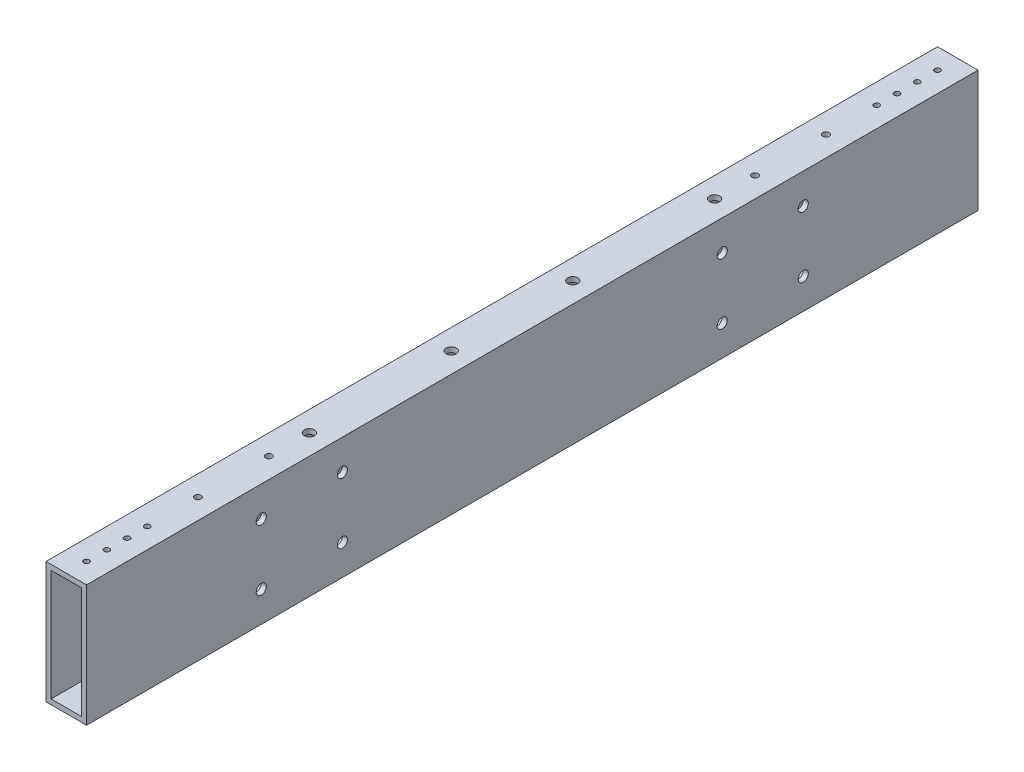
SolidWorks part; units mm, degrees
ref_plane "Front Plane" through (0, 0, 0) normal (0, 0, 1) x (1, 0, 0)
ref_plane "Top Plane" through (0, 0, 0) normal (0, 1, 0) x (1, 0, 0)
ref_plane "Right Plane" through (0, 0, 0) normal (1, 0, 0) x (0, 0, -1)
sketch "Sketch1" plane through (0, 0, 0) normal (0, 0, 1) x (1, 0, 0)
  line L0 (9.525, 34.925) -> (-9.525, 34.925)
  line L1 (12.7, 38.1) -> (-12.7, 38.1)
  line L2 (12.7, 38.1) -> (12.7, -38.1)
  line L3 (12.7, -38.1) -> (-12.7, -38.1)
  line L4 (-12.7, 38.1) -> (-12.7, -38.1)
  line L5 (12.7, 38.1) -> (-12.7, -38.1) construction
  line L6 (12.7, -38.1) -> (-12.7, 38.1) construction
  line L7 (-9.525, 34.925) -> (-9.525, -34.925)
  line L8 (9.525, -34.925) -> (-9.525, -34.925)
  line L9 (9.525, 34.925) -> (9.525, -34.925)
  point P0 (0, 0)
  dimension "D1" = 76.2
  dimension "D2" = 25.4
  dimension "D3" = 3.175
extrude "Boss-Extrude1" add sketch "Sketch1" along normal mid plane 558.8
sketch "Sketch2" plane through (0, 38.1, 0) normal (0, 1, 0) x (1, 0, 0)
  line L0 (12.7, 279.4) -> (-12.7, 279.4) construction
  line L1 (66.7546, 0) -> (-110.9827, 0) construction
  line L2 (12.7, -279.4) -> (-12.7, -279.4) construction
  circle A0 centre (0, 266.7) radius 1.7272
  circle A1 centre (0, 254) radius 1.7272
  circle A2 centre (0, 241.3) radius 1.7272
  circle A3 centre (0, 228.6) radius 1.7272
  circle A4 centre (0, -266.7) radius 1.7272
  circle A5 centre (0, -254) radius 1.7272
  circle A6 centre (0, -241.3) radius 1.7272
  circle A7 centre (0, -228.6) radius 1.7272
  circle A9 centre (0, -241.3) radius 1.7272
  point P22 (0, -279.4)
  point P26 (0, 279.4)
  dimension "D1" = 3.4544
  dimension "D4" = 3.4544
  dimension "D2" = 12.7
  dimension "D5" = 12.7
  dimension "D6" = 12.7
  dimension "D3" = 4
sketch "Sketch3" plane through (0, -38.1, 0) normal (0, -1, 0) x (1, 0, 0)
  line L2 (9.525, 279.4) -> (-9.525, 279.4) construction
  circle A0 centre (0, 266.7) radius 1.7272
  circle A1 centre (0, 241.3) radius 1.7272
  circle A2 centre (0, 215.9) radius 1.7272
  circle A3 centre (0, 190.5) radius 1.7272
  circle A4 centre (0, 165.1) radius 1.7272
  circle A5 centre (0, 139.7) radius 1.7272
  circle A6 centre (0, 114.3) radius 1.7272
  circle A7 centre (0, 88.9) radius 1.7272
  circle A8 centre (0, 63.5) radius 1.7272
  circle A9 centre (0, 38.1) radius 1.7272
  circle A10 centre (0, 12.7) radius 1.7272
  circle A11 centre (0, -12.7) radius 1.7272
  circle A12 centre (0, -38.1) radius 1.7272
  circle A13 centre (0, -63.5) radius 1.7272
  circle A14 centre (0, -88.9) radius 1.7272
  circle A15 centre (0, -114.3) radius 1.7272
  circle A16 centre (0, -139.7) radius 1.7272
  circle A17 centre (0, -165.1) radius 1.7272
  circle A18 centre (0, -190.5) radius 1.7272
  circle A19 centre (0, -215.9) radius 1.7272
  circle A20 centre (0, -241.3) radius 1.7272
  circle A21 centre (0, -266.7) radius 1.7272
  point P6 (0, 279.4)
  dimension "D1" = 3.4544
  dimension "D2" = 12.7
  dimension "D4" = 25.4
  dimension "D3" = 22
extrude "Cut-Extrude2" cut sketch "Sketch3" against normal blind 6.35
hole_wizard "1/4 (0.25) Diameter Hole1" positions "Sketch9" profile "Sketch8" hole size "1/4" standard "ANSI Inch"
sketch "Sketch9" plane through (-12.7, 0, 0) normal (-1, 0, 0) x (0, 0, 1)
  line L0 (-119.0625, -19.05) -> (119.0625, -19.05) construction
  line L2 (279.4, -38.1) -> (-279.4, -38.1) construction
  line L3 (279.4, 38.1) -> (-279.4, 38.1) construction
  line L4 (-127, 0) -> (127, 0) construction
  point P10 (-119.0625, -19.05)
  point P11 (119.0625, -19.05)
  point P25 (-119.0625, 19.05)
  point P27 (119.0625, 19.05)
  point P34 (0, -19.05)
  point P168 (169.8625, 19.05)
  point P170 (169.8625, -19.05)
  point P174 (-169.8625, 19.05)
  point P176 (-169.8625, -19.05)
  dimension "D1" = 238.125
  dimension "D2" = 19.05
  dimension "D3" = 254
  dimension "D4" = 19.05
  dimension "D5" = 19.05
  dimension "D6" = 50.8
  dimension "D7" = 50.8
sketch "Sketch8" plane through (-12.7, -19.05, -119.0625) normal (0, 1, 0) x (0, 0, 1)
  line L0 (0, 0) -> (0, 27.3077)
  line L1 (0, 27.3077) -> (3.175, 25.4)
  line L2 (3.175, 25.4) -> (3.175, 0)
  line L5 (3.175, 0) -> (0, 0)
  line L10 (0, 27.3077) -> (-3.175, 25.4) construction
  line L11 (0, -6.35) -> (0, 107.95) construction
  dimension "Hole Dia." = 6.35
  dimension "Hole Depth" = 25.4
  dimension "Drill Angle" = 118
hole_wizard "1/4 (0.25) Diameter Hole2" positions "Sketch12" profile "Sketch13" hole size "1/4" standard "ANSI Inch" end condition through all
sketch "Sketch12" plane through (0, 38.1, 0) normal (0, 1, 0) x (1, 0, 0)
  line L0 (12.7, -279.4) -> (-12.7, -279.4) construction
  line L1 (0, 38.1) -> (0, -38.1) construction
  point P2 (0, 127)
  point P7 (0, -127)
  point P20 (0, -38.1)
  point P22 (0, 38.1)
  point P27 (0, -279.4)
  point P32 (0, 0)
  dimension "D1" = 127
  dimension "D2" = 127
  dimension "D7" = 76.2
sketch "Sketch13" plane through (0, 38.1, -127) normal (1, 0, 0) x (0, 0, 1)
  line L0 (0, 0) -> (0, 76.2)
  line L1 (0, 76.2) -> (3.175, 76.2)
  line L2 (3.175, 76.2) -> (3.175, 0)
  line L5 (3.175, 0) -> (0, 0)
  line L11 (0, -6.35) -> (0, 107.95) construction
  dimension "Thru Hole Dia." = 6.35
  dimension "Thru Hole Depth" = 76.2
extrude "Cut-Extrude3" cut sketch "Sketch2" against normal blind 5.08 contours A0 | A1 | A2 | A3 | A4 | A5 | A6 | A7 region at (0, 38.1, -266.7) region at (0, 38.1, -254) region at (0, 38.1, -241.3) region at (0, 38.1, -228.6) region at (0, 38.1, 266.7) region at (0, 38.1, 254) region at (0, 38.1, 241.3) region at (0, 38.1, 228.6)
hole_wizard "#10-32 Tapped Hole1" positions "Sketch15" profile "Sketch14" tap size "#10-32" standard "ANSI Inch"
sketch "Sketch15" plane through (0, 38.1, 0) normal (0, 1, 0) x (1, 0, 0)
  line L0 (12.7, 279.4) -> (-12.7, 279.4) construction
  line L1 (12.7, -279.4) -> (-12.7, -279.4) construction
  point P0 (0, -196.85)
  point P2 (0, -152.4)
  point P4 (0, 152.4)
  point P6 (0, 196.85)
  dimension "D1" = 82.55
  dimension "D2" = 127
  dimension "D3" = 82.55
  dimension "D4" = 127
sketch "Sketch14" plane through (0, 38.1, 196.85) normal (1, 0, 0) x (0, 0, 1)
  line L0 (0, 0) -> (0, 14.9293)
  line L1 (0, 14.9293) -> (2.0193, 13.716)
  line L2 (2.0193, 13.716) -> (2.0193, 0)
  line L5 (2.0193, 0) -> (0, 0)
  line L10 (0, 14.9293) -> (-2.0193, 13.716) construction
  line L11 (0, -6.35) -> (0, 107.95) construction
  dimension "Tap Drill Dia." = 4.0386
  dimension "Tap Drill Depth" = 13.716
  dimension "Drill Angle" = 118
cosmetic thread "Hole Thread1" parameters "D1"=3.175, "D2"=4.826
cosmetic thread "Hole Thread2" parameters "D1"=3.175, "D2"=4.826
cosmetic thread "Hole Thread3" parameters "D1"=3.175, "D2"=4.826
cosmetic thread "Hole Thread4" parameters "D1"=3.175, "D2"=4.826
